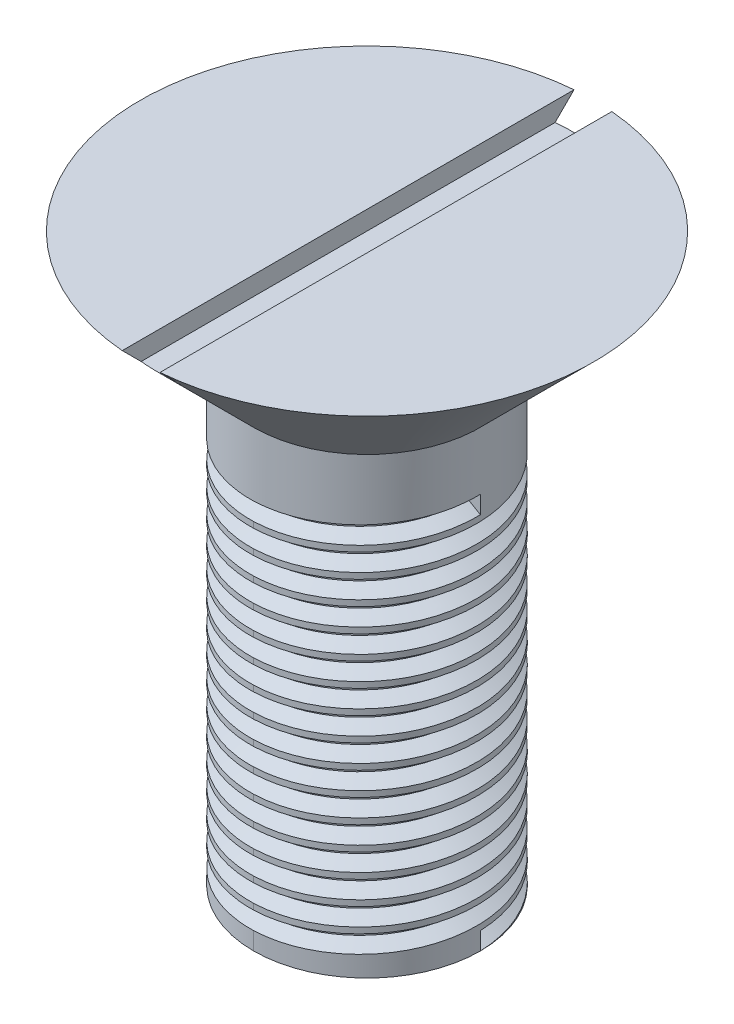
SolidWorks part; units mm, degrees
ref_plane "Front Plane" through (0, 0, 0) normal (0, 0, 1) x (1, 0, 0)
ref_plane "Top Plane" through (0, 0, 0) normal (0, 1, 0) x (1, 0, 0)
ref_plane "Right Plane" through (0, 0, 0) normal (1, 0, 0) x (0, 0, -1)
sketch "Sketch2" plane through (0, 0, 0) normal (0, 0, 1) x (1, 0, 0)
  line L0 (0, 53.7538) -> (0, -87.5223) construction
  line L1 (0, -52.7201) -> (0, -22.7201)
  line L2 (0, -52.7201) -> (6, -52.7201)
  line L3 (6, -52.7201) -> (6, -28.7201)
  line L5 (6, -28.7201) -> (12, -22.7201)
  line L6 (0, -22.7201) -> (12, -22.7201)
  dimension "D1" = 6
revolve "Revolve1" add sketch "Sketch2" angle 360 about L0
thread "Thread1" pitch 1.25 method cut profile "Thread Profile1" start angle 0, offset 0, length 20, pitch 1.25, diameter 12
ref_plane "Plane1" through (6, -52.7201, 0) normal (0, 0, -1) x (-1, 0, 0)
sketch "Thread Profile1" plane through (6, -52.7201, 0) normal (0, 0, -1) x (-1, 0, 0)
  line L0 (0, 0) -> (0, 1.25) construction
  line L1 (0, 0) -> (0.6766, 0.3906)
  line L2 (0.6766, 0.3906) -> (0.6766, 0.5469)
  line L3 (0.6766, 0.5469) -> (0, 0.9375)
  line L4 (0.6766, 0.4687) -> (0, 0.4687) construction
  line L11 (0, 0) -> (0, 0.9375)
  point P2 (0, 0)
  dimension "Pitch" = 1.25
  dimension "Profile_Angle" = 60
  dimension "Profile_Land" = 0.1562
  dimension "Profile_Height" = 0.6766
sketch "Sketch3" plane through (0, -22.7201, 0) normal (0, 1, 0) x (1, 0, 0)
  line L1 (-1, 15) -> (1, 15)
  line L2 (-1, 15) -> (-1, -15)
  line L3 (-1, -15) -> (1, -15)
  line L4 (1, 15) -> (1, -15)
  line L5 (-1, 15) -> (1, -15) construction
  line L6 (-1, -15) -> (1, 15) construction
  point P0 (0, 0)
  dimension "D1" = 30
  dimension "D2" = 2
extrude "Cut-Extrude1" cut sketch "Sketch3" against normal blind 1
